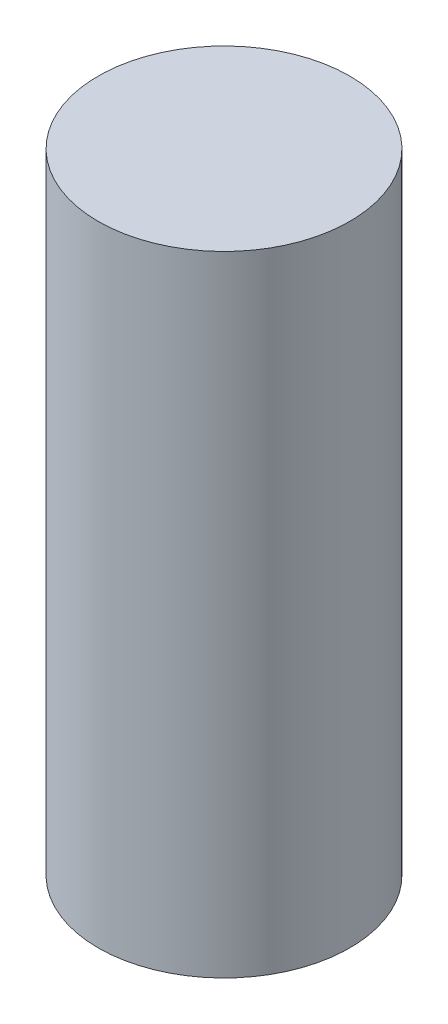
SolidWorks part; units mm, degrees
ref_plane "Front Plane" through (0, 0, 0) normal (0, 0, 1) x (1, 0, 0)
ref_plane "Top Plane" through (0, 0, 0) normal (0, 1, 0) x (1, 0, 0)
ref_plane "Right Plane" through (0, 0, 0) normal (1, 0, 0) x (0, 0, -1)
sketch "Sketch1" plane through (0, 0, 0) normal (0, 1, 0) x (1, 0, 0)
  circle A0 centre (0, 0) radius 20
  dimension "D1" = 40
extrude "Boss-Extrude1" add sketch "Sketch1" along normal blind 100
sketch "Sketch2" plane through (0, 0, 0) normal (0, -1, 0) x (1, 0, 0)
  circle A0 centre (0, 0) radius 2
extrude "Cut-Extrude1" cut sketch "Sketch2" against normal blind 20
